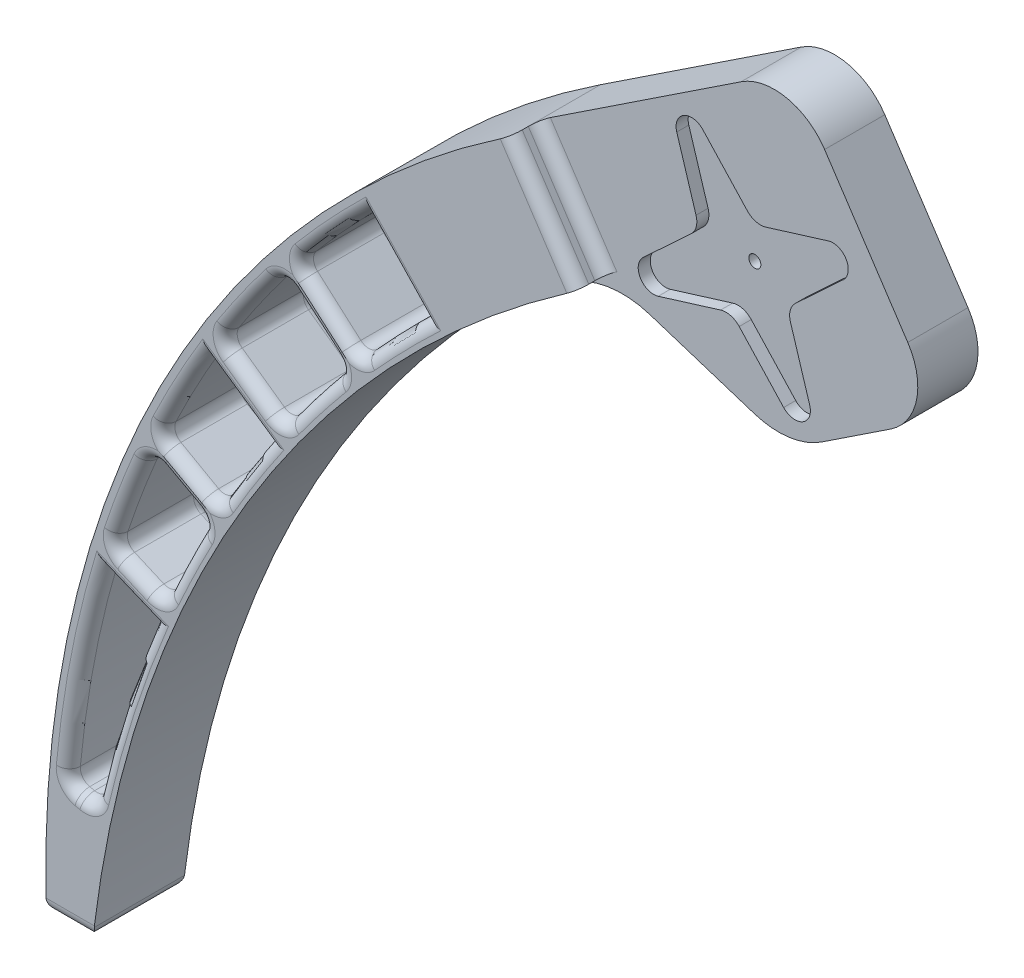
SolidWorks part; units mm, degrees
ref_plane "Plan de face" through (0, 0, 0) normal (0, 0, 1) x (1, 0, 0)
ref_plane "Plan de dessus" through (0, 0, 0) normal (0, 1, 0) x (1, 0, 0)
ref_plane "Plan de droite" through (0, 0, 0) normal (1, 0, 0) x (0, 0, -1)
sketch "Esquisse1" plane through (0, 0, 0) normal (0, 0, 1) x (1, 0, 0)
  line L0 (0, 0) -> (-7.7116, 0)
  line L1 (-7.7116, 0) -> (-7.7116, 150) construction
  line L2 (-7.7116, 150) -> (69.2884, 150) construction
  line L3 (69.2884, 150) -> (80.3349, 133.3274)
  arc A0 (-7.7116, 0) -> (69.2884, 150) centre (164.4344, 6.3951) cw
  arc A1 (80.3349, 133.3274) -> (0, 0) centre (185.1203, -20.676) ccw
  dimension "D1" = 20
  dimension "D2" = 150
  dimension "D3" = 77
extrude "Boss.-Extru.1" add sketch "Esquisse1" along normal blind 15
sketch "Esquisse2" plane through (0, 0, 15) normal (0, 0, 1) x (1, 0, 0)
  line L0 (80.3349, 133.3274) -> (69.2884, 150) construction
  line L1 (-7.7116, 0) -> (0, 0) construction
  line L2 (62.3684, 141.3979) -> (70.9664, 130.2035)
  line L3 (48.6033, 129.7481) -> (58.0983, 119.3958)
  line L4 (70.9454, 147.4991) -> (78.6779, 135.8283)
  line L5 (46.0039, 127.2473) -> (55.6406, 117.1018)
  line L6 (69.2884, 150) -> (70.9454, 147.4991)
  line L7 (78.6779, 135.8283) -> (80.3349, 133.3274)
  line L8 (-7.7116, 0) -> (-4.7116, 0)
  line L9 (-3, 0) -> (-4.7116, 0)
  line L10 (0, 0) -> (-3, 0)
  line L11 (33.8448, 113.9602) -> (43.9728, 105.0081)
  line L12 (31.5886, 111.1559) -> (41.7683, 102.4698)
  line L13 (21.2433, 96.4806) -> (31.4285, 89.2228)
  line L14 (19.3677, 93.4257) -> (29.5014, 86.4679)
  line L15 (10.9988, 77.6405) -> (20.603, 72.2126)
  line L16 (9.5313, 74.393) -> (18.9744, 69.2715)
  line L17 (3.2521, 57.7957) -> (11.6148, 54.1641)
  line L18 (2.2102, 54.4164) -> (10.3026, 51.0688)
  line L19 (-4.2431, 20.0283) -> (0.2206, 19.0409)
  arc A1 (78.6779, 135.8283) -> (-3, 0) centre (188.3019, -22.5641) ccw
  arc A2 (70.9454, 147.4991) -> (-4.7116, 0) centre (165.108, 6.0472) ccw
  arc A3 (69.2884, 150) -> (-7.7116, 0) centre (164.4344, 6.3951) ccw
  arc A4 (69.2884, 150) -> (-7.7116, 0) centre (164.4344, 6.3951) ccw construction
  arc A5 (0, 0) -> (80.3349, 133.3274) centre (185.1203, -20.676) cw
  point P0 (78.6779, 135.8283)
  point P1 (70.9454, 147.4991)
  point P4 (-4.7116, 0)
  point P5 (-3, 0)
  dimension "D13" = 1
  dimension "D14" = 5
  dimension "D15" = 1
  dimension "D1" = 3
  dimension "D2" = 3
  dimension "D3" = 3
  dimension "D4" = 3
  dimension "D5" = 4
  dimension "D6" = 5
  dimension "D7" = 1
  dimension "D8" = 5
  dimension "D9" = 1
  dimension "D10" = 5
  dimension "D11" = 1
  dimension "D12" = 5
  dimension "D16" = 10
extrude "Enlèv. mat.-Extru.3" cut sketch "Esquisse2" against normal up to next contours L2 A2 L3 A1 | L5 A2 L11 A1 | L12 A2 L13 A1 | L14 A2 L15 A1 | L16 A2 L17 A1 | L18 A2 L19 A1
sketch "Esquisse12" plane through (0, 0, 0) normal (0, 0, 1) x (1, 0, 0)
  line L0 (94.143, 112.4867) -> (69.2884, 150)
  line L1 (69.2884, 150) -> (110.9699, 177.6162)
  line L2 (110.9699, 177.6162) -> (135.8245, 140.1029)
  line L3 (135.8245, 140.1029) -> (94.143, 112.4867)
  dimension "D1" = 50
  dimension "D2" = 45
  dimension "D3" = 0
extrude "Boss.-Extru.4" add sketch "Esquisse12" along normal blind 10
sketch "Esquisse27" plane through (0, 0, 15) normal (0, 0, 1) x (1, 0, 0)
  line L0 (47.1881, 129.6841) -> (58.0565, 117.812)
  line L1 (58.0565, 117.812) -> (72.7204, 130.1897)
  line L2 (72.7204, 130.1897) -> (62.3562, 143.5699)
  line L3 (62.3562, 143.5699) -> (47.1881, 129.6841)
extrude "Boss.-Extru.5" add sketch "Esquisse27" against normal blind 15
fillet "Congé8" radius 10 2 edges at (135.8245, 140.1029, 5) (110.9699, 177.6162, 5)
fillet "Congé18" radius 2 1 edges at (74.8117, 141.6637, 10)
sketch "Esquisse24" plane through (82.6638, -34.6024, 10) normal (0, 0, 1) x (0.866, 0.5, 0)
  line L0 (107.5945, 145.7269) -> (90.416, 145.7269) construction
  line L1 (89.8462, 148.2269) -> (107.3962, 152.2269)
  line L2 (107.3962, 139.2269) -> (89.8462, 143.2269)
  arc A0 (107.3962, 139.2269) -> (107.3962, 152.2269) centre (107.5945, 145.7269) ccw
  arc A1 (89.8462, 148.2269) -> (89.8462, 143.2269) centre (90.416, 145.7269) ccw
  dimension "D1" = 18
  dimension "D2" = 13
  dimension "D3" = 5
extrude "Enlèv. mat.-Extru.9" cut sketch "Esquisse24" against normal blind 2
pattern_circular "Répétition circulaire1" count 4 over 270 about axis through (102.9798, 145.3981, 0) along (0, 0, 1) of "Enlèv. mat.-Extru.9"
sketch "Esquisse25" plane through (0, 0, 8) normal (0, 0, 1) x (1, 0, 0)
  circle A0 centre (102.9059, 145.4019) radius 1
  dimension "D1" = 2
extrude "Enlèv. mat.-Extru.10" cut sketch "Esquisse25" against normal through all
sketch "Esquisse26" plane through (0, 0, 10) normal (0, 0, 1) x (1, 0, 0)
  line L0 (80.3349, 133.3274) -> (94.143, 112.4867)
  line L1 (80.3349, 133.3274) -> (94.143, 112.4867) construction
  line L2 (94.143, 112.4867) -> (127.4882, 134.5797) construction
  line L3 (94.143, 112.4867) -> (110.8156, 123.5332)
  line L4 (110.8156, 123.5332) -> (80.3349, 133.3274)
  arc A0 (81.9945, 134.4436) -> (80.3349, 133.3274) centre (185.1203, -20.676) ccw construction
extrude "Enlèv. mat.-Extru.11" cut sketch "Esquisse26" against normal through all
fillet "Congé21" radius 3 4 edges at (110.2612, 143.447, 9) (104.9309, 152.6794, 9) (95.6985, 147.3491, 9) (101.0288, 138.1167, 9)
fillet "Congé22" radius 15 1 edges at (80.3349, 133.3274, 5)
fillet "Congé26" radius 13 1 edges at (110.8156, 123.5332, 5)
fillet "Congé27" radius 2 52 edges at (4.5624, 35.275, 0) (4.5624, 35.275, 15) (-1.9038, 37.3889, 15) (-1.9038, 37.3889, 0) (15.1298, 61.7981, 0) (15.1298, 61.7981, 15) (6.1749, 66.1764, 0) (6.1749, 66.1764, 15) (24.8967, 79.4374, 0) (24.8967, 79.4374, 15) (14.9756, 85.6432, 15) (14.9756, 85.6432, 0) (36.4539, 95.9591, 0) (36.4539, 95.9591, 15) (26.222, 103.955, 0) (26.222, 103.955, 15) (-7.7116, 0, 7.5) (-3.8558, 0, 15) (0, 0, 7.5) (-3.8558, 0, 0) (0.2206, 19.0409, 7.5) (-2.0112, 19.5346, 15) (-4.2431, 20.0283, 7.5) (-2.0112, 19.5346, 0) (11.6148, 54.1641, 7.5) (7.4334, 55.9799, 15) (3.2521, 57.7957, 7.5) (7.4334, 55.9799, 0) (14.2529, 71.8322, 15) (14.2529, 71.8322, 0) (9.5313, 74.393, 7.5) (18.9744, 69.2715, 7.5) (20.603, 72.2126, 7.5) (15.8009, 74.9266, 15) (10.9988, 77.6405, 7.5) (15.8009, 74.9266, 0) (31.4285, 89.2228, 7.5) (26.3359, 92.8517, 15) (21.2433, 96.4806, 7.5) (26.3359, 92.8517, 0) (36.6785, 106.8128, 15) (36.6785, 106.8128, 0) (31.5886, 111.1559, 7.5) (41.7683, 102.4698, 7.5) (49.6748, 111.1822, 0) (49.6748, 111.1822, 15) (39.7482, 120.765, 0) (39.7482, 120.765, 15) (38.9088, 109.4842, 15) (43.9728, 105.0081, 7.5) (33.8448, 113.9602, 7.5) (38.9088, 109.4842, 0)
fillet "Congé29" radius 2 1 edges at (74.8117, 141.6637, 15)
fillet "Congé30" radius 1 6 edges at (24.433, 89.9479, 0) (24.433, 89.9479, 15) (6.2515, 52.7446, 0) (6.2515, 52.7446, 15) (50.8222, 122.1746, 0) (50.8222, 122.1746, 15)
